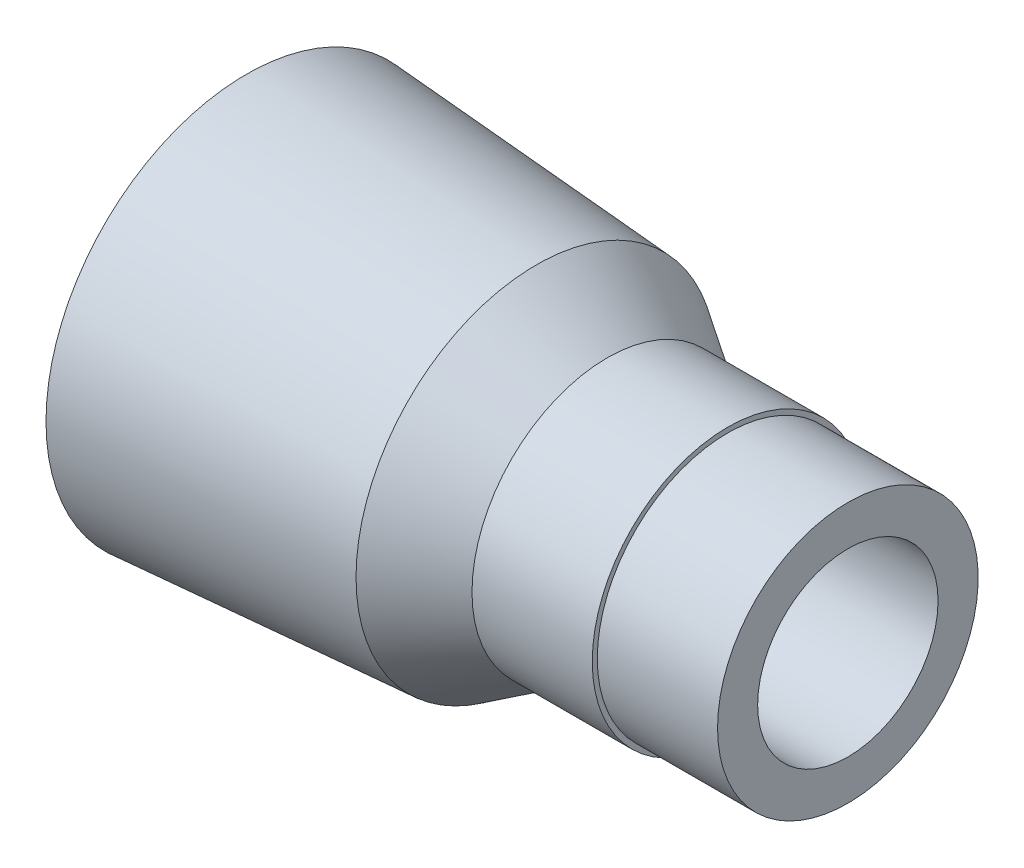
SolidWorks part; units mm, degrees
material "PE High Density"
ref_plane "Front Plane" through (0, 0, 0) normal (0, 0, 1) x (1, 0, 0)
ref_plane "Top Plane" through (0, 0, 0) normal (0, 1, 0) x (1, 0, 0)
ref_plane "Right Plane" through (0, 0, 0) normal (1, 0, 0) x (0, 0, -1)
sketch "Sketch1" plane through (0, 0, 0) normal (0, 1, 0) x (1, 0, 0)
  line L0 (0, 0) -> (0, -10)
  line L1 (0, -10) -> (14.4655, -9)
  line L3 (18, -6.75) -> (24, -6.75)
  line L4 (24, -6.75) -> (24, -6.5)
  line L5 (24, -6.5) -> (30, -6.5)
  line L6 (30, -6.5) -> (30, -4.5)
  line L7 (0, 0) -> (30, 0)
  line L8 (15, -7.5) -> (15, -3)
  line L9 (0, -7.5) -> (15, -7.5)
  line L10 (15, -3) -> (19, -3)
  line L11 (19, -3) -> (19, -4.5)
  line L12 (19, -4.5) -> (30, -4.5)
  line L13 (30, -4.5) -> (30, 0)
  line L14 (18, -6.75) -> (14.4655, -9)
  line L16 (0, 0) -> (30, 0) construction
  dimension "D1" = 7.5
  dimension "D2" = 14.5
  dimension "D3" = 6
  dimension "D4" = 6
  dimension "D5" = 10
  dimension "D6" = 11
  dimension "D7" = 4.5
  dimension "D8" = 6.5
  dimension "D9" = 6.75
  dimension "D10" = 30
  dimension "D11" = 4
  dimension "D12" = 9
  dimension "D13" = 3
revolve "Revolve2" add sketch "Sketch1" angle 360 about L16 region at (15.108, 0, 6.7257)
sketch "Sketch7" plane through (0, 0, 0) normal (-1, 0, 0) x (0, 0, 1)
  circle A1 centre (0, 0) radius 10 construction
  circle A2 centre (0, 0) radius 9.9
  dimension "D2" = 0.1
extrude "Cut-Extrude4" cut sketch "Sketch7" against normal blind 2 draft 2
sketch "Sketch9" plane through (2, 0, 0) normal (-1, 0, 0) x (0, 0, 1)
  line L0 (-6.5426, -3.6667) -> (-8.5753, -4.8059)
  line L1 (-7.3445, -1.5193) -> (-9.6629, -1.8059)
  arc A0 (-9.6629, -1.8059) -> (-8.5753, -4.8059) centre (0, 0) ccw
  arc A1 (-7.3445, -1.5193) -> (-6.5426, -3.6667) centre (0, 0) ccw
  circle A2 centre (0, 0) radius 7.5 construction
  point P4 (0, 0)
  point P10 (0, 0)
  point P11 (-7.3445, -1.5193)
  dimension "D1" = 3
extrude "Boss-Extrude2" add sketch "Sketch9" along normal blind 2
thread "Thread1" pitch 0.25 method cut profile "Thread Profile1" start angle 0, offset 0, length 0, pitch 2, diameter 15
ref_plane "Plane2" through (15, 0, 7.5) normal (0, 1, 0) x (0, 0, -1)
sketch "Thread Profile1" plane through (15, 0, 7.5) normal (0, 1, 0) x (0, 0, -1)
  line L0 (0, 0) -> (0, 0.25) construction
  line L11 (0, 0) -> (0, 0.2187)
  line L12 (0, 0.2187) -> (-0.1353, 0.1406)
  line L13 (-0.1353, 0.1406) -> (-0.1353, 0.0781)
  line L15 (-0.1353, 0.0781) -> (0, 0)
  line L17 (-0.1353, 0.1094) -> (0, 0.1094) construction
  point P2 (0, 0)
  dimension "Pitch" = 0.25
  dimension "Profile_Angle" = 60
  dimension "Profile_Land" = 0.0625
  dimension "Profile_Height" = 0.1353
pattern_circular "CirPattern1" count 8 over 360 about axis through (0, 0, 0) along (1, 0, 0) of "Boss-Extrude2" reverse direction yes
